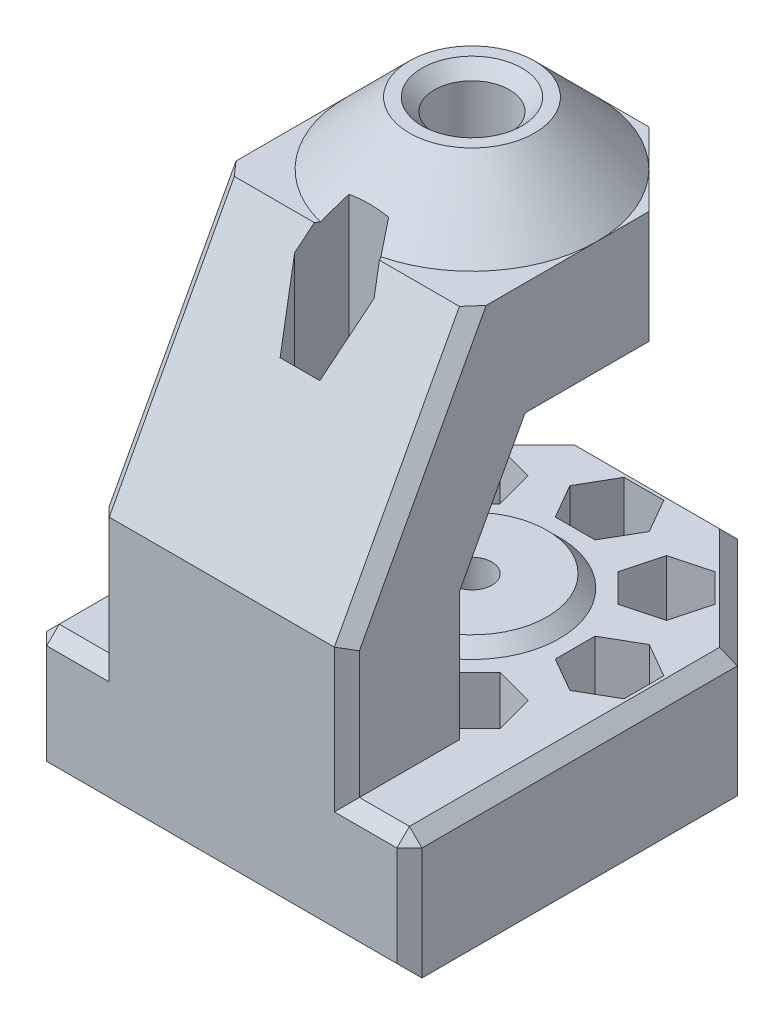
SolidWorks part; units mm, degrees
ref_plane "Alzado" through (0, 0, 0) normal (0, 0, 1) x (1, 0, 0)
ref_plane "Planta" through (0, 0, 0) normal (0, 1, 0) x (1, 0, 0)
ref_plane "Vista lateral" through (0, 0, 0) normal (1, 0, 0) x (0, 0, -1)
sketch "Croquis1" plane through (0, 0, 0) normal (0, 1, 0) x (1, 0, 0)
  line L0 (-15, -6.2132) -> (-15, -20)
  line L1 (6.2132, -15) -> (15, -6.2132) construction
  line L2 (15, -6.2132) -> (15, 6.2132)
  line L3 (15, 6.2132) -> (6.2132, 15)
  line L4 (6.2132, 15) -> (-6.2132, 15)
  line L5 (-6.2132, 15) -> (-15, 6.2132)
  line L6 (-15, 6.2132) -> (-15, -6.2132)
  line L7 (-15, -6.2132) -> (-6.2132, -15) construction
  line L8 (-6.2132, -15) -> (6.2132, -15) construction
  line L9 (-15, -20) -> (15, -20)
  line L10 (15, -20) -> (15, -6.2132)
  circle A0 centre (0, 0) radius 1.6
  circle A1 centre (0, 0) radius 15 construction
  dimension "D1" = 3.2
  dimension "D2" = 30
  dimension "D3" = 20
extrude "Saliente-Extruir1" add sketch "Croquis1" along normal blind 10
sketch "Croquis2" plane through (-15, 0, 0) normal (-1, 0, 0) x (0, 0, 1)
  line L1 (-6.2132, 10) -> (20, 10) construction
  line L2 (10, 20) -> (4.6215, 30)
  line L3 (4.6215, 30) -> (-10, 30)
  line L4 (-10, 30) -> (-10, 39)
  line L6 (-10, 39) -> (10, 39)
  line L8 (10, 39) -> (20, 20.4076)
  line L9 (0, 0) -> (0, 60.5511) construction
  line L10 (20, 20.4076) -> (20, 10)
  line L11 (20, 10) -> (10, 10)
  line L12 (10, 10) -> (10, 20)
  point P11 (0, 39)
  point P12 (10, 15)
  dimension "D1" = 20
  dimension "D2" = 9
  dimension "D3" = 10
  dimension "D4" = 10
  dimension "D5" = 10
  dimension "D6" = 9
  dimension "D7" = 10
extrude "Saliente-Extruir2" add sketch "Croquis2" against normal blind 30
sketch "Croquis12" plane through (0, 0, 10) normal (0, 0, -1) x (-1, 0, 0)
  line L1 (-6.2132, 10) -> (6.2132, 10)
  line L2 (-6.2132, 10) -> (-6.2132, 14.8559)
  line L3 (-6.2132, 14.8559) -> (6.2132, 14.8559)
  line L4 (6.2132, 10) -> (6.2132, 14.8559)
extrude "Cortar-Extruir7" cut sketch "Croquis12" against normal blind 3.5
sketch "Croquis3" plane through (0, 39, 0) normal (0, 1, 0) x (1, 0, 0)
  line L0 (-10, -4.1421) -> (-9.9995, -20)
  line L3 (-9.9995, -20) -> (10, -20)
  line L5 (10, -20) -> (10, -4.1421)
  line L6 (4.1421, 10) -> (-4.1421, 10)
  line L7 (-4.1421, 10) -> (-10, 4.1421)
  line L8 (15, -20) -> (-15, -20) construction
  line L9 (-10, 4.1421) -> (-10, -4.1421)
  line L10 (-10, -4.1421) -> (-4.1421, -10) construction
  line L11 (-4.1421, -10) -> (4.1421, -10) construction
  line L12 (4.1421, -10) -> (10, -4.1421) construction
  line L13 (10, -4.1421) -> (10, 4.1421)
  line L14 (10, 4.1421) -> (4.1421, 10)
  circle A0 centre (0, 0) radius 1.6
  circle A1 centre (0, 0) radius 10 construction
  circle A3 centre (0, 0) radius 10 construction
  dimension "D1" = 3.2
  dimension "D2" = 20
extrude "Cortar-Extruir1" cut sketch "Croquis3" against normal up to surface (29 mm away) flip side to cut up to face at (0, 10, 2.4574)
sketch "Croquis4" plane through (0, 39, 0) normal (0, 1, 0) x (1, 0, 0)
  circle A0 centre (0, 0) radius 10
extrude "Saliente-Extruir3" add sketch "Croquis4" along normal blind 5
chamfer "Chaflán1" distance 5 angle 45 1 edges at (0, 44, 10)
sketch "Croquis5" plane through (0, 44, 0) normal (0, 1, 0) x (1, 0, 0)
  circle A0 centre (0, 0) radius 3
  dimension "D1" = 6
sketch "Croquis6" plane through (0, 0, 0) normal (0, -1, 0) x (1, 0, 0)
  circle A0 centre (0, 11) radius 1.6
  circle A1 centre (0, 0) radius 1.6 construction
  circle A2 centre (7.7782, 7.7782) radius 1.6
  circle A3 centre (11, 0) radius 1.6
  circle A4 centre (7.7782, -7.7782) radius 1.6
  circle A5 centre (0, -11) radius 1.6
  circle A6 centre (-7.7782, -7.7782) radius 1.6
  circle A7 centre (-11, 0) radius 1.6
  circle A8 centre (-7.7782, 7.7782) radius 1.6
  point P21 (0, 0)
  dimension "D1" = 3.2
  dimension "D2" = 11
  dimension "D3" = 8
extrude "Cortar-Extruir3" cut sketch "Croquis6" against normal up to surface (10 mm away) up to face at (0, 10, 7.4695)
sketch "Croquis8" plane through (0, 10, 0) normal (0, 1, 0) x (1, 0, 0)
  circle A0 centre (0, 0) radius 6
  circle A1 centre (0, 0) radius 1.6
  dimension "D1" = 12
extrude "Saliente-Extruir4" add sketch "Croquis8" along normal blind 1
chamfer "Chaflán2" distance 1 angle 45 1 edges at (0, 10, 6)
extrude "Cortar-Extruir4" cut sketch "Croquis5" against normal up to surface (33 mm away) up to face at (0, 11, 6)
chamfer "Chaflán3" distance 1 angle 45 18 edges at (10, 25, 7.3107) (10, 15, 10) (-9.9999, 25, 7.3107) (-9.9998, 15, 10) (0, 0, 20) (12.5, 10, 20) (15, 5, 20) (15, 10, 6.8934) (10.6066, 10, -10.6066) (0, 10, -15) (-10.6066, 10, -10.6066) (-15, 10, 6.8934) (-12.4998, 10, 20) (-15, 5, 20) (10, 15.2038, 20) (-9.9995, 15.2038, 20) (10, 29.7038, 15) (-9.9997, 29.7038, 15) first distance on face at (10, 27.6408, 7.0479) first distance on face at (-9.9998, 24.8009, 10.3632) first distance on face at (0, 0, 9.4) first distance on face at (0, 10, 7) first distance on face at (15, 5, 6.8934) first distance on face at (-15, 5, 6.8934)
sketch "Croquis9" plane through (0, 0, 0) normal (0, -1, 0) x (1, 0, 0)
  line L0 (-10.0235, -5.5328) -> (-10.8454, -8.6)
  line L1 (-3.1754, -11) -> (-1.5877, -13.75)
  line L2 (-1.5877, -13.75) -> (1.5877, -13.75)
  line L3 (1.5877, -13.75) -> (3.1754, -11)
  line L4 (3.1754, -11) -> (1.5877, -8.25)
  line L5 (1.5877, -8.25) -> (-1.5877, -8.25)
  line L6 (-1.5877, -8.25) -> (-3.1754, -11)
  line L7 (-10.8454, -8.6) -> (-8.6, -10.8454)
  line L8 (-8.6, -10.8454) -> (-5.5328, -10.0235)
  line L9 (-5.5328, -10.0235) -> (-4.7109, -6.9563)
  line L10 (-4.7109, -6.9563) -> (-6.9563, -4.7109)
  line L11 (-6.9563, -4.7109) -> (-10.0235, -5.5328)
  line L12 (-11, 3.1754) -> (-13.75, 1.5877)
  line L13 (-13.75, 1.5877) -> (-13.75, -1.5877)
  line L14 (-13.75, -1.5877) -> (-11, -3.1754)
  line L15 (-11, -3.1754) -> (-8.25, -1.5877)
  line L16 (-8.25, -1.5877) -> (-8.25, 1.5877)
  line L17 (-8.25, 1.5877) -> (-11, 3.1754)
  line L18 (-5.5328, 10.0235) -> (-8.6, 10.8454)
  line L19 (-8.6, 10.8454) -> (-10.8454, 8.6)
  line L20 (-10.8454, 8.6) -> (-10.0235, 5.5328)
  line L21 (-10.0235, 5.5328) -> (-6.9563, 4.7109)
  line L22 (-6.9563, 4.7109) -> (-4.7109, 6.9563)
  line L23 (-4.7109, 6.9563) -> (-5.5328, 10.0235)
  line L24 (3.1754, 11) -> (1.5877, 13.75)
  line L25 (1.5877, 13.75) -> (-1.5877, 13.75)
  line L26 (-1.5877, 13.75) -> (-3.1754, 11)
  line L27 (-3.1754, 11) -> (-1.5877, 8.25)
  line L28 (-1.5877, 8.25) -> (1.5877, 8.25)
  line L29 (1.5877, 8.25) -> (3.1754, 11)
  line L30 (10.0235, 5.5328) -> (10.8454, 8.6)
  line L31 (10.8454, 8.6) -> (8.6, 10.8454)
  line L32 (8.6, 10.8454) -> (5.5328, 10.0235)
  line L33 (5.5328, 10.0235) -> (4.7109, 6.9563)
  line L34 (4.7109, 6.9563) -> (6.9563, 4.7109)
  line L35 (6.9563, 4.7109) -> (10.0235, 5.5328)
  line L36 (11, -3.1754) -> (13.75, -1.5877)
  line L37 (13.75, -1.5877) -> (13.75, 1.5877)
  line L38 (13.75, 1.5877) -> (11, 3.1754)
  line L39 (11, 3.1754) -> (8.25, 1.5877)
  line L40 (8.25, 1.5877) -> (8.25, -1.5877)
  line L41 (8.25, -1.5877) -> (11, -3.1754)
  line L42 (5.5328, -10.0235) -> (8.6, -10.8454)
  line L43 (8.6, -10.8454) -> (10.8454, -8.6)
  line L44 (10.8454, -8.6) -> (10.0235, -5.5328)
  line L45 (10.0235, -5.5328) -> (6.9563, -4.7109)
  line L46 (6.9563, -4.7109) -> (4.7109, -6.9563)
  line L47 (4.7109, -6.9563) -> (5.5328, -10.0235)
  circle A0 centre (0, -11) radius 2.75 construction
  circle A2 centre (-7.7782, -7.7782) radius 2.75 construction
  circle A3 centre (-11, 0) radius 2.75 construction
  circle A4 centre (-7.7782, 7.7782) radius 2.75 construction
  circle A5 centre (0, 11) radius 2.75 construction
  circle A6 centre (7.7782, 7.7782) radius 2.75 construction
  circle A7 centre (11, 0) radius 2.75 construction
  circle A8 centre (7.7782, -7.7782) radius 2.75 construction
  point P68 (0, 0)
  dimension "D1" = 5.5
  dimension "D2" = 8
extrude "Cortar-Extruir5" cut sketch "Croquis9" against normal blind 15 from offset 5 offset against normal yes
sketch "Croquis13" plane through (0, 10, -10) normal (0, -1, 0) x (-1, 0, 0)
  line L1 (-3.1754, -21) -> (-1.5877, -23.75)
  line L2 (-1.5877, -23.75) -> (1.5877, -23.75)
  line L3 (1.5877, -23.75) -> (3.1754, -21)
  line L4 (3.1754, -21) -> (1.5877, -18.25)
  line L5 (1.5877, -18.25) -> (-1.5877, -18.25)
  line L6 (-1.5877, -18.25) -> (-3.1754, -21)
  circle A0 centre (0, -21) radius 2.75 construction
  dimension "D1" = 5.5
extrude "Cortar-Extruir8" cut sketch "Croquis13" against normal through all
chamfer "Chaflán4" distance 1 angle 45 1 edges at (0, 44, 3)
sketch "Croquis10" plane through (0, 0, 0) normal (0, -1, 0) x (1, 0, 0)
  line L1 (3.1754, 0) -> (1.5877, 2.75)
  line L2 (1.5877, 2.75) -> (-1.5877, 2.75)
  line L3 (-1.5877, 2.75) -> (-3.1754, 0)
  line L4 (-3.1754, 0) -> (-1.5877, -2.75)
  line L5 (-1.5877, -2.75) -> (1.5877, -2.75)
  line L6 (1.5877, -2.75) -> (3.1754, 0)
  circle A0 centre (0, 0) radius 2.75 construction
  dimension "D1" = 5.5
extrude "Cortar-Extruir6" cut sketch "Croquis10" against normal blind 3.5
